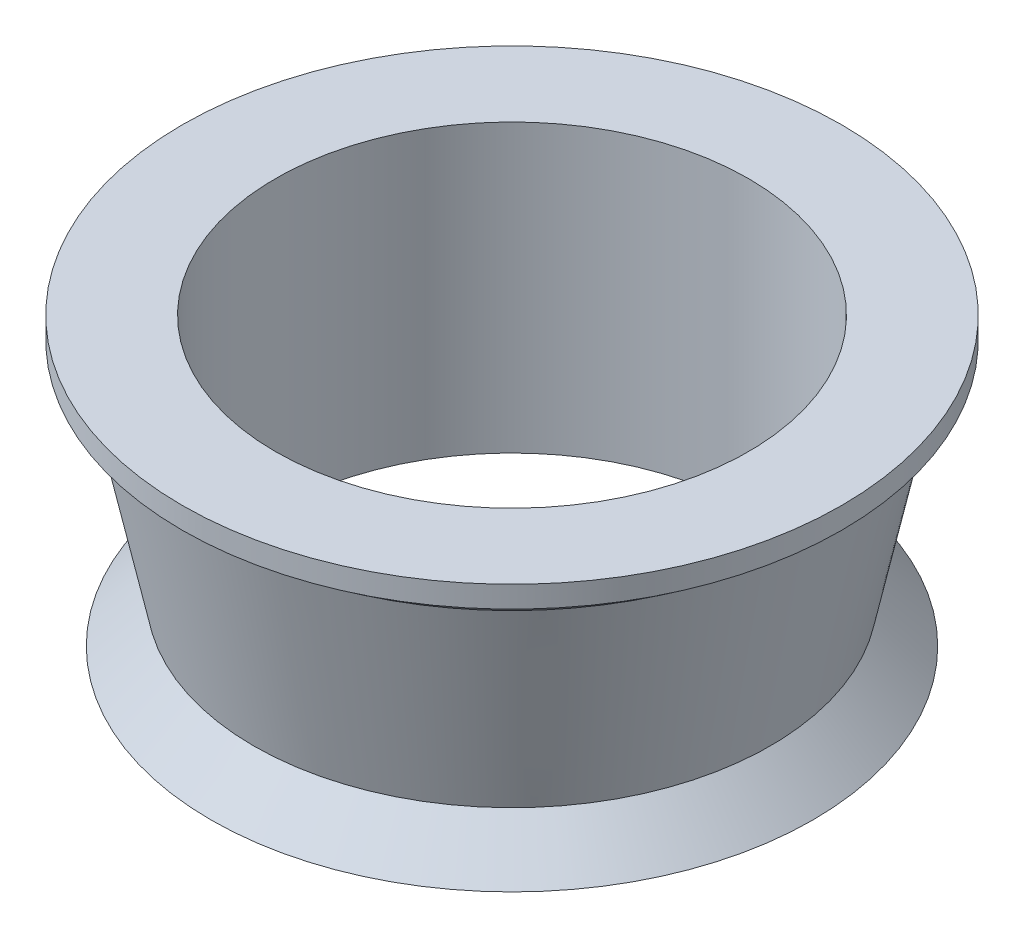
SolidWorks part; units mm, degrees
ref_plane "Front Plane" through (0, 0, 0) normal (0, 0, 1) x (1, 0, 0)
ref_plane "Top Plane" through (0, 0, 0) normal (0, 1, 0) x (1, 0, 0)
ref_plane "Right Plane" through (0, 0, 0) normal (1, 0, 0) x (0, 0, -1)
sketch "Sketch1" plane through (0, 0, 0) normal (0, 1, 0) x (1, 0, 0)
  circle A0 centre (0, 0) radius 10.5
  circle A1 centre (0, 0) radius 8.25
  dimension "D1" = 21
  dimension "D2" = 16.5
extrude "Boss-Extrude1" add sketch "Sketch1" along normal blind 7
chamfer "Chamfer1" distance 7 angle 12 1 edges at (0, 0, 10.5) first distance on face at (0, 7, 10.5)
sketch "Sketch4" plane through (0, 0, 0) normal (0, -1, 0) x (1, 0, 0)
  circle A0 centre (0, 0) radius 8.25
  circle A1 centre (0, 0) radius 11
  circle A2 centre (0, 0) radius 8.25 construction
  dimension "D1" = 22
extrude "Boss-Extrude2" add sketch "Sketch4" along normal blind 1.5
sketch "Sketch5" plane through (0, 7, 0) normal (0, 1, 0) x (1, 0, 0)
  circle A0 centre (0, 0) radius 8.25
  circle A1 centre (0, 0) radius 11.5
  circle A2 centre (0, 0) radius 8.25 construction
  dimension "D1" = 23
extrude "Boss-Extrude3" add sketch "Sketch5" along normal blind 1.5
chamfer "Chamfer2" distance 2 angle 45 1 edges at (0, 0, -11)
chamfer "Chamfer3" distance 0.75 angle 53 1 edges at (0, 7, 11.5) first distance on face at (0, 8.5, 11.5)
